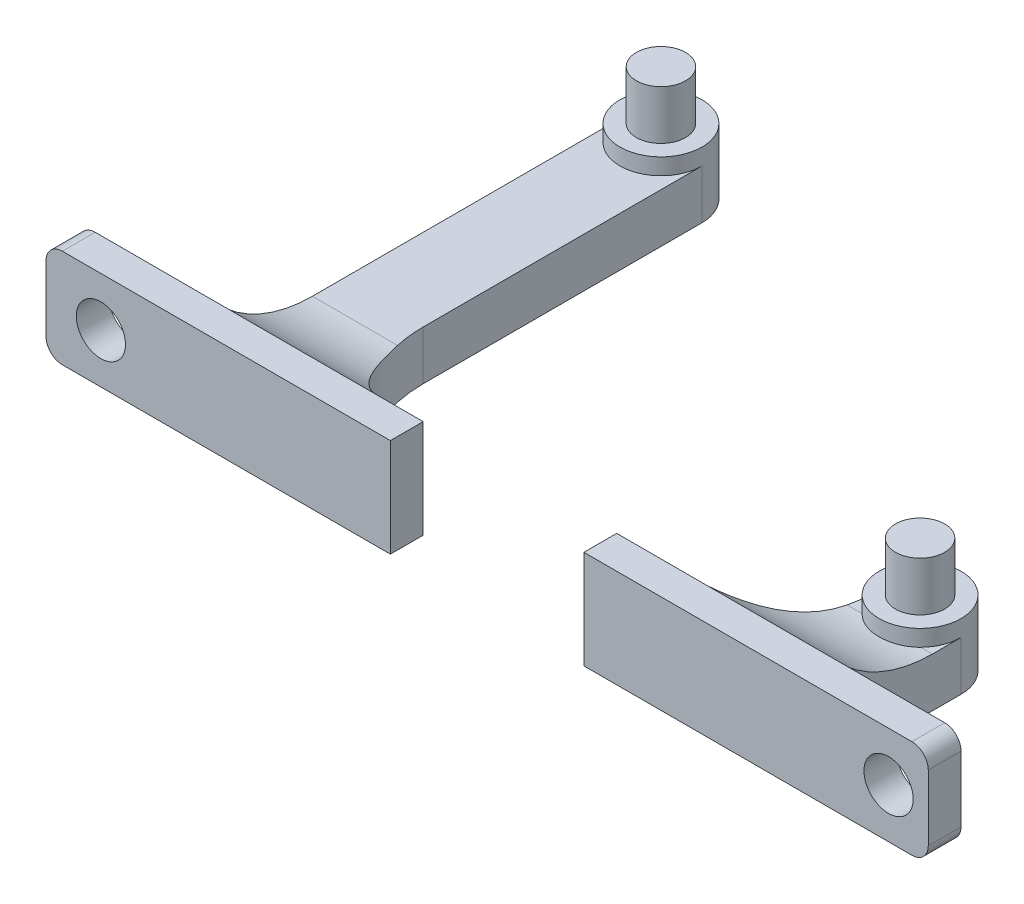
SolidWorks part; units mm, degrees
ref_plane "Front Plane" through (0, 0, 0) normal (0, 0, 1) x (1, 0, 0)
ref_plane "Top Plane" through (0, 0, 0) normal (0, 1, 0) x (1, 0, 0)
ref_plane "Right Plane" through (0, 0, 0) normal (1, 0, 0) x (0, 0, -1)
sketch "Sketch1" plane through (0, 0, 0) normal (0, 1, 0) x (1, 0, 0)
  line L1 (24.25, 11.5) -> (-24.25, 11.5)
  line L2 (24.25, 11.5) -> (24.25, -11.5)
  line L3 (24.25, -11.5) -> (-24.25, -11.5)
  line L4 (-24.25, 11.5) -> (-24.25, -11.5)
  line L5 (24.25, 11.5) -> (-24.25, -11.5) construction
  line L6 (24.25, -11.5) -> (-24.25, 11.5) construction
  line L7 (-18.55, 8.5) -> (-13.55, 8.5)
  line L8 (-18.55, 8.5) -> (-18.55, -16.5)
  line L9 (-18.55, -16.5) -> (-13.55, -16.5)
  line L10 (-13.55, 8.5) -> (-13.55, -16.5)
  line L11 (14.25, -8.5) -> (19.25, -8.5)
  line L12 (14.25, -8.5) -> (14.25, -16.5)
  line L13 (14.25, -16.5) -> (19.25, -16.5)
  line L14 (19.25, -8.5) -> (19.25, -16.5)
  circle A0 centre (-16.05, 8.5) radius 1.5
  circle A1 centre (16.75, -8.5) radius 1.5
  circle A2 centre (-16.05, 8.5) radius 2.5
  circle A3 centre (16.75, -8.5) radius 2.5
  point P0 (0, 0)
  dimension "D3" = 3
  dimension "D4" = 3
  dimension "D5" = 8.2
  dimension "D6" = 3
  dimension "D7" = 7.5
  dimension "D8" = 3
  dimension "D1" = 48.5
  dimension "D2" = 23
  dimension "D10" = 5
  dimension "D11" = 5
  dimension "D9" = 1
extrude "Boss-Extrude1" add sketch "Sketch1" along normal blind 3 contours A2 L8 L3 L10 | L10 L3 L8 L9 | L14 L3 L12 L13 | A3 L12 L3 L14 region at (16.75, 0, 14) region at (16.75, 0, 11.4417) region at (-16.05, 0, 2.4731) region at (-16.05, 0, 14)
extrude "Boss-Extrude2" add sketch "Sketch1<3>" along normal blind 4 contours L7 A2 A0 | L7 A2 A0 | L11 A3 A1 | L11 A3 A1 region at (16.75, 0, 10.9441) region at (18.75, 0, 8.4441) region at (-16.05, 0, -10.9441) region at (-18.05, 0, -8.4441)
sketch "Sketch1<3>" plane through (0, 0, 0) normal (0, 1, 0) x (1, 0, 0) same geometry as "Sketch1"
extrude "Boss-Extrude3" add sketch "Sketch1<4>" along normal blind 7 contours L7 A0 | L7 A0 | L11 A1 | L11 A1 region at (16.75, 0, 9.1366) region at (16.75, 0, 7.8634) region at (-16.05, 0, -9.1366) region at (-16.05, 0, -7.8634)
sketch "Sketch1<4>" plane through (0, 0, 0) normal (0, 1, 0) x (1, 0, 0) same geometry as "Sketch1"
sketch "Sketch2" plane through (0, 0, 16.5) normal (0, 0, 1) x (1, 0, 0)
  line L0 (19.25, 3) -> (19.25, 0) construction
  line L1 (-26.55, 0) -> (27.25, 0)
  line L2 (-26.55, 0) -> (-26.55, 6)
  line L3 (-26.55, 6) -> (27.25, 6)
  line L4 (27.25, 0) -> (27.25, 6)
  line L5 (-18.55, 3) -> (-18.55, 0) construction
  dimension "D1" = 6
  dimension "D2" = 8
  dimension "D3" = 8
extrude "Boss-Extrude4" add sketch "Sketch2" along normal blind 2
fillet "Fillet2" radius 1 4 edges at (-26.55, 0, 17.5) (-26.55, 6, 17.5) (27.25, 0, 17.5) (27.25, 6, 17.5)
fillet "Fillet3" radius 8 4 edges at (14.25, 1.5, 16.5) (16.75, 3, 16.5) (-16.05, 3, 16.5) (-13.55, 1.5, 16.5)
fillet "Fillet4" radius 1 2 edges at (19.25, 3, 16.5) (-18.55, 3, 16.5)
sketch "Sketch4" plane through (0, 6, 0) normal (0, 1, 0) x (1, 0, 0)
  line L0 (26.25, -18.5) -> (-25.55, -18.5) construction
  line L1 (-5.55, -16.5) -> (6.25, -16.5)
  line L2 (-5.55, -16.5) -> (-5.55, -18.5)
  line L3 (-5.55, -18.5) -> (6.25, -18.5)
  line L4 (6.25, -16.5) -> (6.25, -18.5)
extrude "Cut-Extrude2" cut sketch "Sketch4" against normal through all
sketch "Sketch5" plane through (0, 0, 16.5) normal (0, 0, -1) x (-1, 0, 0)
  line L0 (26.55, 3) -> (-30.1707, 3) construction
  line L1 (26.55, 5) -> (26.55, 1) construction
  circle A0 centre (23.2034, 3) radius 1.5
  circle A1 centre (-24.8294, 3) radius 1.5
  dimension "D1" = 3
  dimension "D2" = 3
extrude "Cut-Extrude3" cut sketch "Sketch5" against normal blind 2
